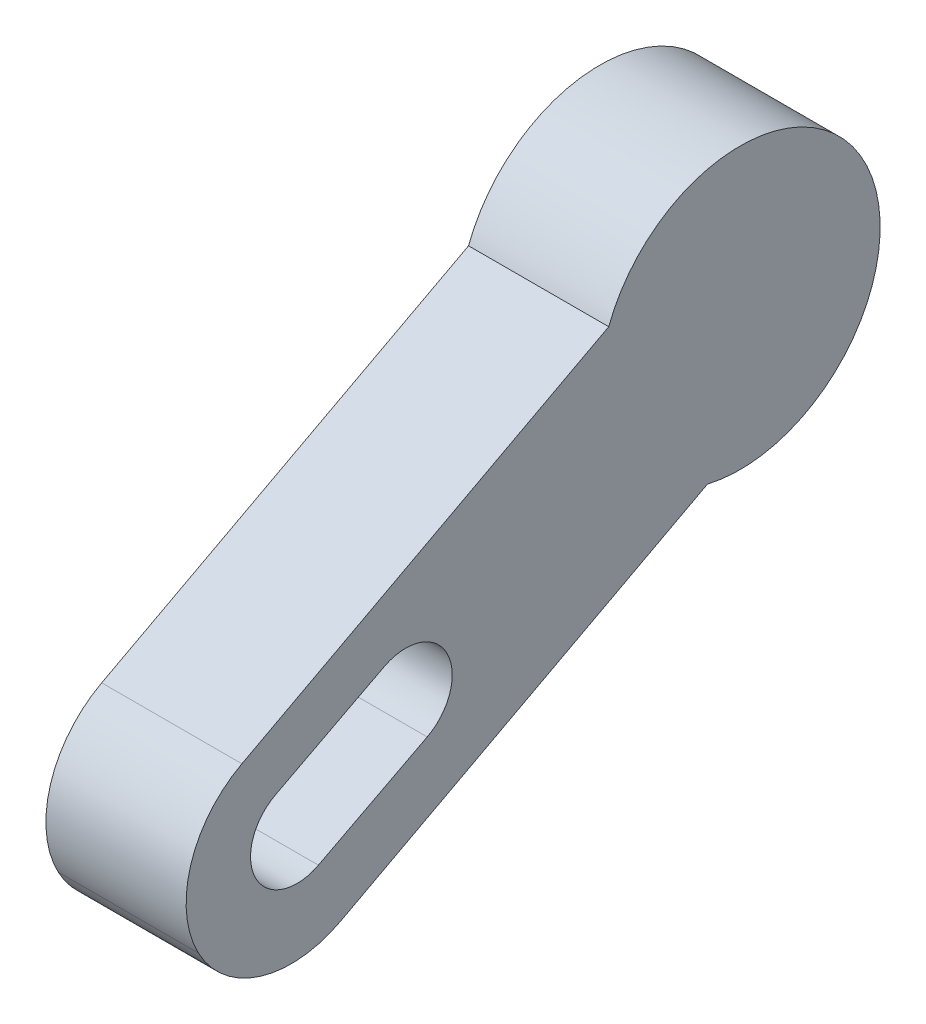
SolidWorks part; units mm, degrees
ref_plane "Front Plane" through (0, 0, 0) normal (0, 0, 1) x (1, 0, 0)
ref_plane "Top Plane" through (0, 0, 0) normal (0, 1, 0) x (1, 0, 0)
ref_plane "Right Plane" through (0, 0, 0) normal (1, 0, 0) x (0, 0, -1)
sketch "Sketch5" plane through (0, 0, 0) normal (1, 0, 0) x (0, 0, -1)
  circle A0 centre (0, 0) radius 4
  dimension "D1" = 8
extrude "Boss-Extrude2" add sketch "Sketch5" along normal blind 4
sketch "Sketch6" plane through (0, 0, 0) normal (1, 0, 0) x (0, 0, -1)
  line L0 (-1.4084, 2.6488) -> (1.4084, -2.6488)
  line L1 (-1.4084, 2.6488) -> (-16.86, -5.5669)
  line L2 (1.4084, -2.6488) -> (-14.0432, -10.8646)
  line L3 (-16.86, -5.5669) -> (-14.0432, -10.8646)
  line L4 (0, 0) -> (-15.0686, 0) construction
  point P0 (0, 0)
  dimension "D1" = 6
  dimension "D2" = 17.5
  dimension "D3" = 28
extrude "Boss-Extrude3" add sketch "Sketch6" along normal blind 4
sketch "Sketch7" plane through (0, 0, 0) normal (-1, 0, 0) x (0, 0, 1)
  circle A0 centre (0, 0) radius 2.6
  dimension "D1" = 5.2
extrude "Cut-Extrude3" cut sketch "Sketch7" against normal blind 2.5
sketch "Sketch8" plane through (2.5, 0, 0) normal (-1, 0, 0) x (0, 0, 1)
  line L0 (1.6, -0.75) -> (-1.6, -0.75)
  line L1 (1.6, -0.75) -> (1.6, 0.75)
  line L2 (-1.6, -0.75) -> (-1.6, 0.75)
  line L3 (1.6, 0.75) -> (0.65, 0.75)
  line L5 (0.65, 0.75) -> (0.65, 1.25)
  line L6 (-0.65, 0.75) -> (-0.65, 1.25)
  line L7 (0.65, 1.25) -> (-0.65, 1.25)
  line L8 (-0.65, 0.75) -> (-1.6, 0.75)
  line L9 (1.6, 0) -> (-1.6, 0) construction
  line L10 (-9.3611, 0) -> (9.3611, 0) construction
  point P10 (0, 0)
  point P17 (0, 0)
  dimension "D1" = 1.5
  dimension "D2" = 3.2
  dimension "D3" = 1.3
  dimension "D4" = 0.5
  dimension "D5" = 0
extrude "Boss-Extrude4" add sketch "Sketch8" along normal blind 2.5
fillet "Fillet1" radius 0.3 4 edges at (1.25, -0.75, 1.6) (1.25, 0.75, 1.6) (1.25, -0.75, -1.6) (1.25, 0.75, -1.6)
sketch "Sketch10" plane through (4, 0, 0) normal (1, 0, 0) x (0, 0, -1)
  line L0 (-9.5354, -4.9638) -> (-12.6399, -6.5799) construction
  line L1 (-8.9235, -6.1391) -> (-12.0281, -7.7552)
  line L2 (-10.1472, -3.7885) -> (-13.2517, -5.4046)
  line L3 (15.7034, 0) -> (-15.7034, 0) construction
  line L4 (0, 0) -> (-44350.5417, -23087.4307) construction
  arc A0 (-8.9235, -6.1391) -> (-10.1472, -3.7885) centre (-9.5354, -4.9638) ccw
  arc A1 (-13.2517, -5.4046) -> (-12.0281, -7.7552) centre (-12.6399, -6.5799) ccw
  point P2 (-11.0876, -5.7719)
  point P11 (0, 0)
  dimension "D1" = 27.5
  dimension "D2" = 2.65
  dimension "D3" = 3.5
  dimension "D4" = 12.5
extrude "Cut-Extrude4" cut sketch "Sketch10" against normal up to next
fillet "Fillet2" radius 3 2 edges at (2, -10.8646, 14.0432) (2, -5.5669, 16.86)
